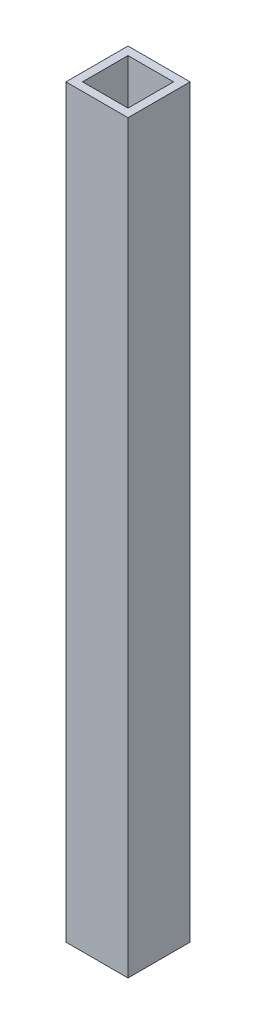
SolidWorks part; units mm, degrees
ref_plane "Front Plane" through (0, 0, 0) normal (0, 0, 1) x (1, 0, 0)
ref_plane "Top Plane" through (0, 0, 0) normal (0, 1, 0) x (1, 0, 0)
ref_plane "Right Plane" through (0, 0, 0) normal (1, 0, 0) x (0, 0, -1)
sketch "Sketch1" plane through (0, 0, 0) normal (0, 1, 0) x (1, 0, 0)
  line L0 (2, 2) -> (2, 13)
  line L1 (0, 0) -> (15, 0)
  line L2 (0, 0) -> (0, 15)
  line L3 (0, 15) -> (15, 15)
  line L4 (15, 0) -> (15, 15)
  line L5 (2, 13) -> (13, 13)
  line L6 (13, 2) -> (13, 13)
  line L7 (2, 2) -> (13, 2)
  dimension "D1" = 15
  dimension "D2" = 2
extrude "Boss-Extrude1" add sketch "Sketch1" along normal blind 180
